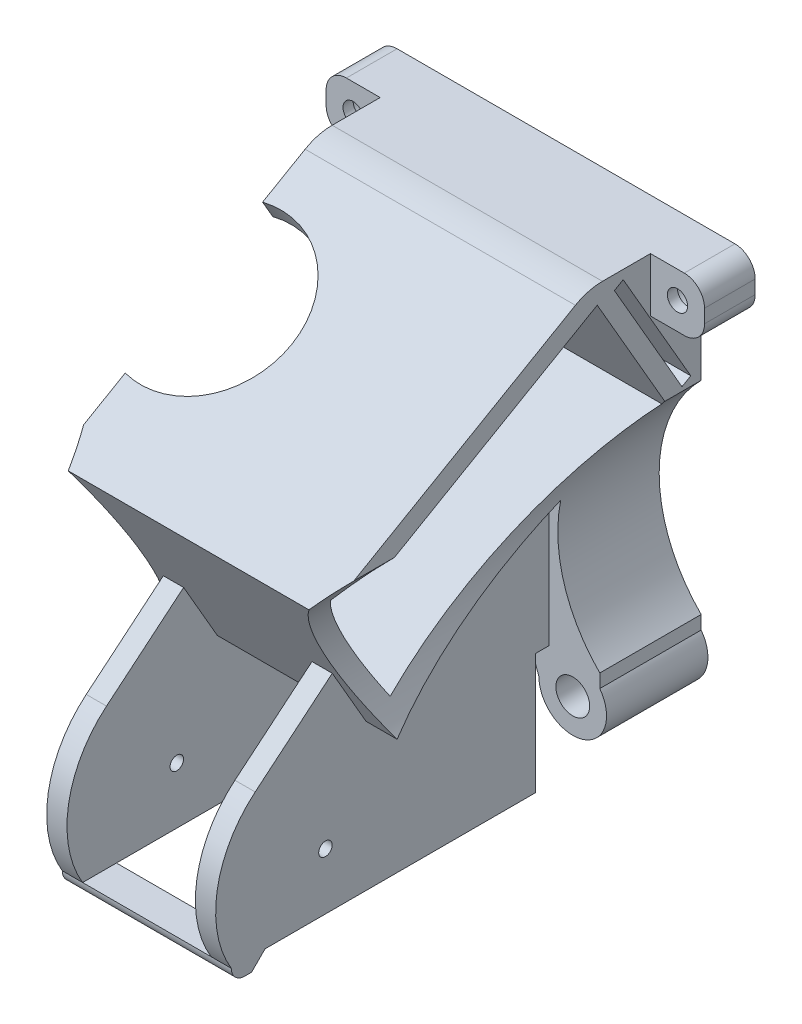
SolidWorks part; units mm, degrees
material "ABS"
ref_plane "Alzado" through (0, 0, 0) normal (0, 0, 1) x (1, 0, 0)
ref_plane "Planta" through (0, 0, 0) normal (0, 1, 0) x (1, 0, 0)
ref_plane "Vista lateral" through (0, 0, 0) normal (1, 0, 0) x (0, 0, -1)
sketch "Croquis1" plane through (0, 0, 0) normal (0, 0, 1) x (1, 0, 0)
  line L0 (-152.0308, 99.9536) -> (-112.0308, 99.9536)
  line L1 (-152.0308, 99.9536) -> (-152.0308, 39.9536)
  line L2 (-152.0308, 39.9536) -> (-112.0308, 39.9536)
  line L3 (-112.0308, 99.9536) -> (-112.0308, 39.9536)
  circle A2 centre (-148.0308, 44.9536) radius 2.5
  circle A3 centre (-116.0308, 44.9536) radius 2.5
  dimension "D1" = 60
  dimension "D3" = 5
  dimension "D4" = 5
  dimension "D2" = 40
  dimension "D5" = 32
  dimension "D6" = 4
  dimension "D7" = 5
ref_plane "Plano1" through (0, 0, 0) normal (0, 0, 1) x (1, 0, 0)
sketch "Croquis2" plane through (0, 0, 0) normal (0, 0, 1) x (1, 0, 0)
  line L0 (-152.0308, 47.9536) -> (-152.0308, 99.9536)
  line L1 (-152.0308, 99.9536) -> (-152.0308, 39.9536) construction
  line L2 (-152.0308, 99.9536) -> (-112.0308, 99.9536)
  line L3 (-112.0308, 99.9536) -> (-112.0308, 47.9536)
  line L4 (-112.0308, 99.9536) -> (-112.0308, 39.9536) construction
  line L6 (-143.0308, 44.9536) -> (-141.2109, 49.9536)
  line L7 (-141.2109, 49.9536) -> (-122.8506, 49.9536)
  line L8 (-122.8506, 49.9536) -> (-121.0308, 44.9536)
  circle A0 centre (-148.0308, 44.9536) radius 2.5
  circle A1 centre (-116.0308, 44.9536) radius 2.5
  arc A2 (-121.0308, 44.9536) -> (-112.0308, 47.9536) centre (-116.0308, 44.9536) ccw
  arc A3 (-152.0308, 47.9536) -> (-143.0308, 44.9536) centre (-148.0308, 44.9536) ccw
  dimension "D1" = 52
  dimension "D2" = 5
  dimension "D3" = 5
  dimension "D4" = 52
  dimension "D6" = 110
  dimension "D7" = 110
extrude "Saliente-Extruir1" add sketch "Croquis2" along normal blind 3
sketch "Croquis3" plane through (-152.0308, 0, 0) normal (-1, 0, 0) x (0, 0, 1)
  line L0 (3, 99.9536) -> (16.75, 99.9536)
  line L1 (15.3799, 97.2805) -> (4.6299, 78.661)
  line L2 (3, 99.9536) -> (3, 47.9536) construction
  line L3 (3, 99.9536) -> (3, 76.1379)
  line L4 (3, 76.1379) -> (42.101, 53.5629)
  line L5 (4.6299, 78.661) -> (41.003, 57.661)
  line L6 (41.003, 57.661) -> (51.753, 76.2805)
  line L7 (51.753, 76.2805) -> (15.3799, 97.2805)
  line L8 (16.75, 99.9536) -> (55.851, 77.3786)
  line L9 (55.851, 77.3786) -> (42.101, 53.5629)
  dimension "D1" = 27.5
  dimension "D2" = 30
  dimension "D3" = 3
  dimension "D4" = 42
  dimension "D5" = 45.15
  dimension "D6" = 3
  dimension "D7" = 3
extrude "Saliente-Extruir2" add sketch "Croquis3" against normal up to vertex (40 mm away) up to point (-112.0308, 47.9536, 3)
sketch "Croquis4" plane through (0, 0, 3) normal (0, 0, 1) x (1, 0, 0)
  line L0 (-152.0308, 47.9536) -> (-152.0308, 49.9536)
  line L1 (-152.0308, 76.1379) -> (-152.0308, 47.9536) construction
  line L6 (-112.0308, 47.9536) -> (-112.0308, 76.1379) construction
  line L7 (-112.0308, 49.9536) -> (-112.0308, 47.9536)
  line L8 (-152.0308, 49.9536) -> (-148.0308, 49.9536)
  line L9 (-112.0308, 49.9536) -> (-116.0308, 49.9536)
  circle A0 centre (-148.0308, 44.9536) radius 2.5
  circle A2 centre (-116.0308, 44.9536) radius 2.5
  arc A4 (-152.0308, 47.9536) -> (-148.0308, 49.9536) centre (-148.0308, 44.9536) ccw
  arc A6 (-116.0308, 49.9536) -> (-112.0308, 47.9536) centre (-116.0308, 44.9536) ccw
extrude "Saliente-Extruir3" add sketch "Croquis4" along normal blind 12
sketch "Croquis7" plane through (0, 82.2182, 47.4687) normal (0, 0.866, 0.5) x (1, 0, 0)
  line L1 (-112.0308, -9.6791) -> (-152.0308, -9.6791) construction
  line L2 (-152.0308, -9.6791) -> (-152.0308, 35.4709) construction
  circle A0 centre (-149.5308, 14.3209) radius 12
  dimension "D1" = 24
  dimension "D3" = 2.5
extrude "Cortar-Extruir1" cut sketch "Croquis7" against normal up to vertex (3 mm away) up to point (-152.0308, 76.2805, 51.753)
sketch "Croquis10" plane through (0, 0, 0) normal (0, 0, -1) x (-1, 0, 0)
  line L0 (152.0308, 79.9536) -> (152.0308, 49.9536)
  line L1 (112.0308, 47.9536) -> (112.0308, 99.9536) construction
  line L8 (112.0308, 79.9536) -> (112.0308, 49.9536)
  arc A0 (112.0308, 79.9536) -> (112.0308, 49.9536) centre (97.0308, 64.9536) cw
  arc A1 (152.0308, 79.9536) -> (152.0308, 49.9536) centre (167.0308, 64.9536) ccw
  dimension "D1" = 2
  dimension "D2" = 20
extrude "Cortar-Extruir2" cut sketch "Croquis10" against normal up to vertex (55.851 mm away) up to point (-112.0308, 77.3786, 55.851)
sketch "Croquis11" plane through (-152.0308, 0, 0) normal (-1, 0, 0) x (0, 0, 1)
  line L0 (12.8398, 97.881) -> (2.8398, 80.5605)
  line L1 (15.3799, 97.2805) -> (5.3762, 79.9536) construction
  line L2 (41.003, 57.661) -> (4.6299, 78.661) construction
  line L5 (12.8398, 97.881) -> (11.5408, 98.631)
  line L6 (11.5408, 98.631) -> (1.5408, 81.3105)
  line L7 (1.5408, 81.3105) -> (2.8398, 80.5605)
  dimension "D1" = 2.5
  dimension "D2" = 0.75
  dimension "D3" = 20
  dimension "D4" = 1.5
extrude "Cortar-Extruir3" cut sketch "Croquis11" against normal up to vertex (40 mm away) up to point (-112.0308, 99.9536, 16.75)
sketch "Croquis12" plane through (0, 0, 3) normal (0, 0, 1) x (1, 0, 0)
  line L0 (-152.0308, 49.9536) -> (-148.0308, 49.9536)
  line L2 (-121.0308, 44.9536) -> (-122.5308, 49.0748)
  line L3 (-141.5308, 49.0748) -> (-141.5308, 76.1379)
  line L4 (-115.0561, 76.1379) -> (-149.0055, 76.1379) construction
  line L5 (-141.5308, 76.1379) -> (-149.0055, 76.1379)
  line L6 (-143.0308, 44.9536) -> (-141.5308, 49.0748)
  line L11 (-143.0308, 44.9536) -> (-141.2109, 49.9536) construction
  line L12 (-132.0308, 54.4723) -> (-132.0308, 64.1484) construction
  line L13 (-122.5308, 76.1379) -> (-115.0561, 76.1379)
  line L14 (-122.5308, 49.0748) -> (-122.5308, 76.1379)
  line L15 (-112.0308, 49.9536) -> (-116.0308, 49.9536)
  arc A0 (-149.0055, 76.1379) -> (-152.0308, 49.9536) centre (-167.0308, 64.9536) cw
  arc A4 (-148.0308, 49.9536) -> (-143.0308, 44.9536) centre (-148.0308, 44.9536) cw
  arc A5 (-116.0308, 49.9536) -> (-121.0308, 44.9536) centre (-116.0308, 44.9536) ccw
  arc A6 (-115.0561, 76.1379) -> (-112.0308, 49.9536) centre (-97.0308, 64.9536) ccw
  dimension "D1" = 9.5
extrude "Saliente-Extruir7" add sketch "Croquis12" along normal up to vertex up to point (-148.0308, 49.9536, 15)
sketch "Croquis14" plane through (-152.0308, 0, 0) normal (-1, 0, 0) x (0, 0, 1)
  line L0 (15.3799, 97.2805) -> (51.8829, 76.2055)
  line L1 (51.8829, 76.2055) -> (41.1329, 57.586)
  line L2 (41.1329, 57.586) -> (4.6299, 78.661)
  line L3 (4.6299, 78.661) -> (15.3799, 97.2805)
  dimension "D1" = 42.15
  dimension "D2" = 21.5
extrude "Cortar-Extruir4" cut sketch "Croquis14" against normal up to vertex (40 mm away) up to point (-112.0308, 79.9536, 45.391)
sketch "Croquis15" plane through (-141.5308, 0, 0) normal (1, 0, 0) x (0, 0, -1)
  line L1 (-15, 49.0748) -> (-15, 69.2097) construction
  line L2 (-15, 69.2097) -> (-15, 49.7097)
  line L3 (-15, 49.7097) -> (-17, 49.7097)
  line L4 (-17, 49.7097) -> (-17, 31.865)
  line L6 (-66.6618, 36.1662) -> (-59.823, 37.6598) construction
  line L7 (-59.823, 37.6598) -> (-48.0994, 40.2203) construction
  line L8 (-15, 69.2097) -> (-42.02, 53.6097)
  line L9 (-42.02, 53.6097) -> (-47.02, 62.27)
  line L11 (-50.6336, 31.865) -> (-17, 31.865)
  line L12 (-50.6336, 31.865) -> (-62.0368, 31.865)
  line L13 (-47.02, 62.27) -> (-58.5007, 52.7053)
  circle A2 centre (-48.0994, 40.2203) radius 1
  arc A4 (-58.5007, 52.7053) -> (-62.0368, 31.865) centre (-48.0994, 40.2203) ccw
  point P10 (-75.6218, 34.2097)
  dimension "D7" = 12
  dimension "D8" = 19.5
  dimension "D1" = 32.5
  dimension "D2" = 70
  dimension "D3" = 2
  dimension "D6" = 7
extrude "Saliente-Extruir8" add sketch "Croquis15" against normal blind 3
extrude "Saliente-Extruir9" add sketch "Croquis15<2>" along normal blind 3 from surface starting at face at (-122.5308, 60.8743, 9)
sketch "Croquis15<2>" plane through (-141.5308, 0, 0) normal (1, 0, 0) x (0, 0, -1) same geometry as "Croquis15"
fillet "Redondeo2" radius 8 1 edges at (-132.0308, 99.9536, 16.75)
sketch "Croquis32" plane through (0, 0, 0) normal (0, 0, -1) x (-1, 0, 0)
  line L1 (112.0308, 99.9536) -> (107.0308, 99.9536)
  line L2 (112.0308, 99.9536) -> (112.0308, 91.9536)
  line L3 (112.0308, 91.9536) -> (107.0308, 91.9536)
  line L4 (104.0308, 96.9536) -> (104.0308, 94.9536)
  circle A0 centre (108.0308, 95.9536) radius 2.5
  arc A1 (107.0308, 91.9536) -> (104.0308, 94.9536) centre (107.0308, 94.9536) cw
  arc A2 (107.0308, 99.9536) -> (104.0308, 96.9536) centre (107.0308, 96.9536) ccw
  point P9 (104.0308, 91.9536)
  point P12 (104.0308, 99.9536)
  dimension "D3" = 3
  dimension "D1" = 8
  dimension "D2" = 8
extrude "Saliente-Extruir14" add sketch "Croquis32" against normal blind 6
sketch "Croquis33" plane through (0, 0, 6) normal (0, 0, 1) x (1, 0, 0)
  line L1 (-112.0308, 99.9536) -> (-107.0308, 99.9536)
  line L2 (-112.0308, 99.9536) -> (-112.0308, 91.9536)
  line L3 (-112.0308, 91.9536) -> (-107.0308, 91.9536)
  line L4 (-104.0308, 96.9536) -> (-104.0308, 94.9536)
  circle A0 centre (-108.0308, 95.9536) radius 1.5
  arc A1 (-107.0308, 99.9536) -> (-104.0308, 96.9536) centre (-107.0308, 96.9536) cw
  arc A2 (-107.0308, 91.9536) -> (-104.0308, 94.9536) centre (-107.0308, 94.9536) ccw
  point P10 (-104.0308, 99.9536)
  point P13 (-104.0308, 91.9536)
  dimension "D3" = 3
  dimension "D1" = 8
  dimension "D2" = 8
extrude "Saliente-Extruir15" add sketch "Croquis33" along normal blind 1.5
sketch "Croquis34" plane through (0, 99.9536, 0) normal (0, 1, 0) x (1, 0, 0)
  line L0 (-132.0308, -14.6064) -> (-132.0308, 0) construction
  line L1 (-152.0308, -14.6064) -> (-112.0308, -14.6064) construction
  line L2 (-107.0308, 0) -> (-152.0308, 0) construction
ref_plane "Plano4" through (-132.0308, 0, 0) normal (1, 0, 0) x (0, 0, -1)
mirror "Simetría1" about plane through (-132.0308, 0, 0) normal (1, 0, 0) of "Saliente-Extruir15", "Saliente-Extruir14"
sketch "Croquis36" plane through (-144.5308, 0, 0) normal (-1, 0, 0) x (0, 0, 1)
  line L0 (57.0368, 31.865) -> (62.0368, 31.865)
  line L1 (62.0368, 31.865) -> (17, 31.865) construction
  line L4 (59.0368, 29.865) -> (57.0368, 31.865)
  line L5 (59.0368, 29.865) -> (60.0368, 29.865)
  arc A0 (62.0368, 31.865) -> (60.0368, 29.865) centre (60.0368, 31.865) cw
  dimension "D2" = 45
  dimension "D3" = 5
extrude "Saliente-Extruir16" add sketch "Croquis36" against normal up to vertex (25 mm away) up to point (-119.5308, 31.865, 17)
